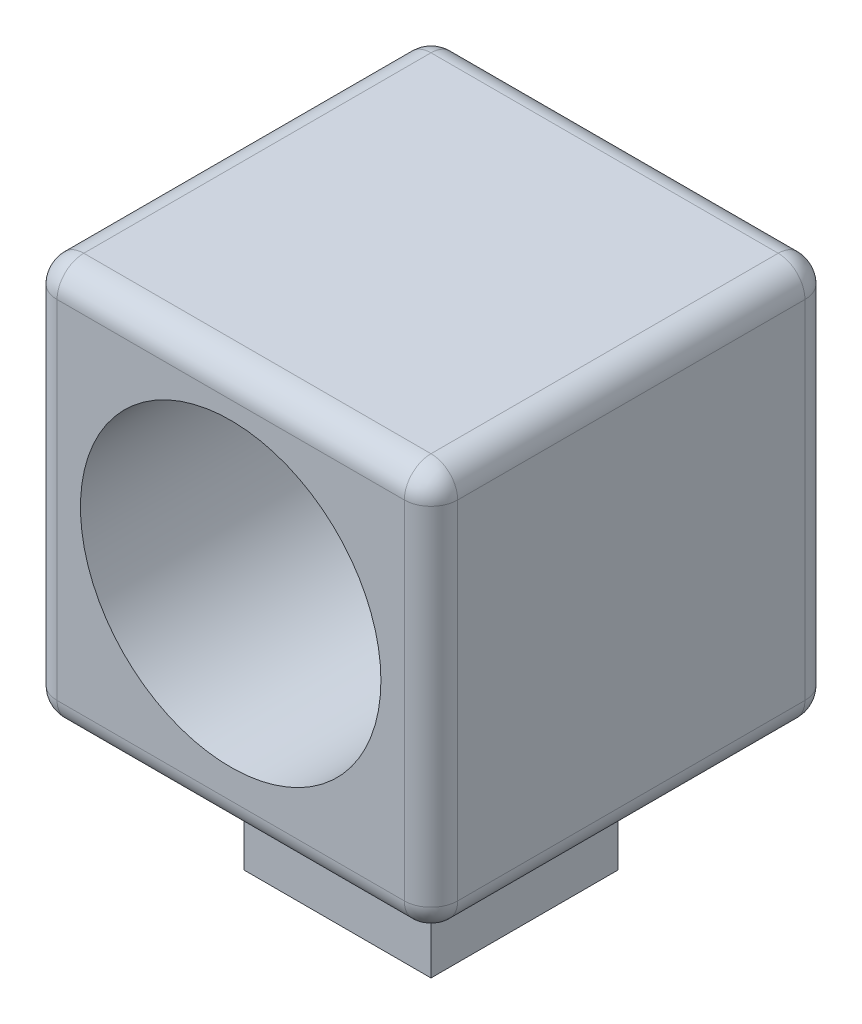
SolidWorks part; units mm, degrees
ref_plane "Front Plane" through (0, 0, 0) normal (0, 0, 1) x (1, 0, 0)
ref_plane "Top Plane" through (0, 0, 0) normal (0, 1, 0) x (1, 0, 0)
ref_plane "Right Plane" through (0, 0, 0) normal (1, 0, 0) x (0, 0, -1)
sketch "Sketch1" plane through (0, 0, 0) normal (0, 1, 0) x (1, 0, 0)
  line L1 (-8.89, -8.89) -> (8.89, -8.89)
  line L2 (-8.89, -8.89) -> (-8.89, 8.89)
  line L3 (-8.89, 8.89) -> (8.89, 8.89)
  line L4 (8.89, -8.89) -> (8.89, 8.89)
  line L5 (-8.89, -8.89) -> (8.89, 8.89) construction
  line L6 (-8.89, 8.89) -> (8.89, -8.89) construction
  point P0 (0, 0)
  dimension "D1" = 17.78
  dimension "D2" = 17.78
extrude "Boss-Extrude1" add sketch "Sketch1" along normal blind 12.7
sketch "Sketch2" plane through (0, 12.7, 0) normal (0, 1, 0) x (1, 0, 0)
  line L1 (-19.05, -19.05) -> (19.05, -19.05)
  line L2 (-19.05, -19.05) -> (-19.05, 19.05)
  line L3 (-19.05, 19.05) -> (19.05, 19.05)
  line L4 (19.05, -19.05) -> (19.05, 19.05)
  line L5 (-19.05, -19.05) -> (19.05, 19.05) construction
  line L6 (-19.05, 19.05) -> (19.05, -19.05) construction
  point P0 (0, 0)
  dimension "D1" = 38.1
  dimension "D2" = 38.1
extrude "Boss-Extrude2" add sketch "Sketch2" along normal blind 38.1
sketch "Sketch3" plane through (0, 0, 19.05) normal (0, 0, 1) x (1, 0, 0)
  circle A0 centre (0, 32.2842) radius 14.2875
  dimension "D1" = 28.575
extrude "Cut-Extrude1" cut sketch "Sketch3" against normal blind 38.1
fillet "Fillet1" radius 2.54 12 edges at (19.05, 50.8, 0) (19.05, 12.7, 0) (-19.05, 50.8, 0) (-19.05, 12.7, 0) (19.05, 31.75, -19.05) (0, 50.8, -19.05) (-19.05, 31.75, -19.05) (0, 12.7, -19.05) (-19.05, 31.75, 19.05) (0, 50.8, 19.05) (19.05, 31.75, 19.05) (0, 12.7, 19.05)
